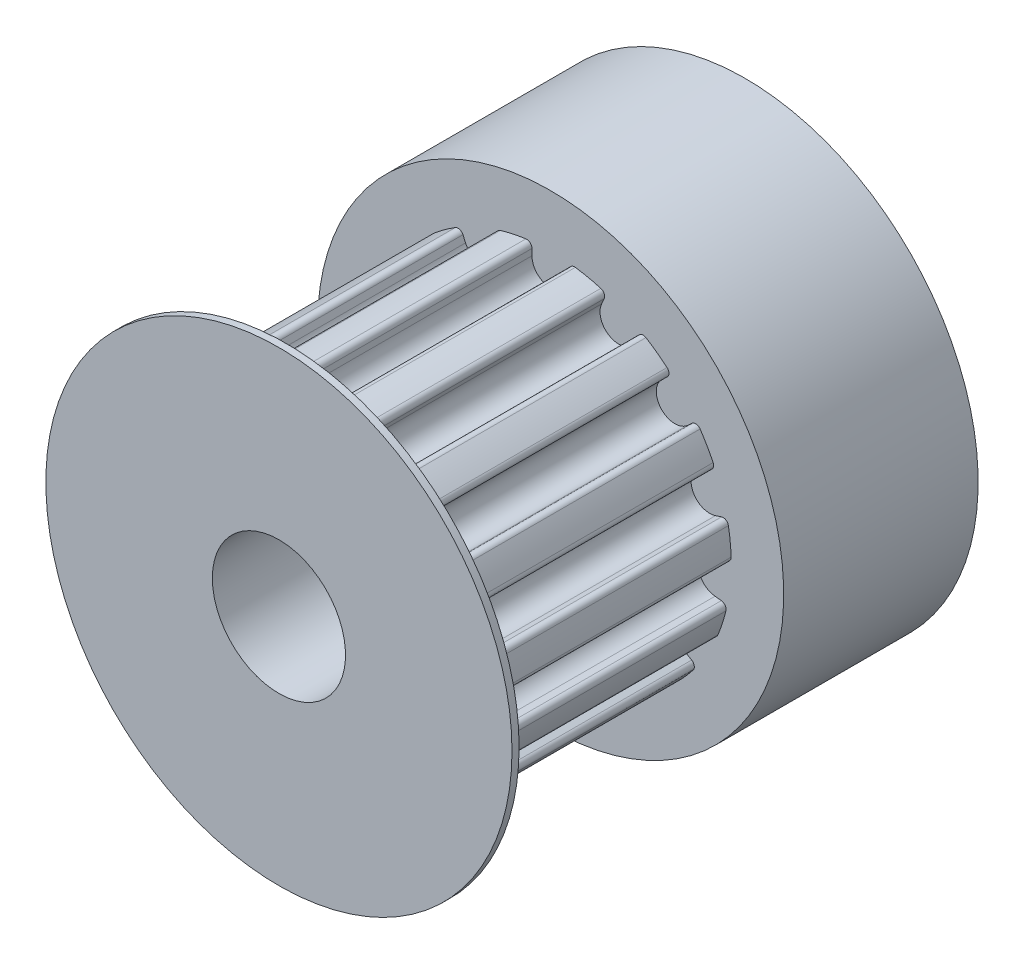
SolidWorks part; units mm, degrees
ref_plane "Front" through (0, 0, 0) normal (0, 0, 1) x (1, 0, 0)
ref_plane "Top" through (0, 0, 0) normal (0, 1, 0) x (1, 0, 0)
ref_plane "Right" through (0, 0, 0) normal (1, 0, 0) x (0, 0, -1)
sketch "support-front-body" plane through (0, 0, 0) normal (0, 0, 1) x (1, 0, 0)
  line L0 (0, 0) -> (0, 6.78) construction
  line L1 (0, 0) -> (0, -6.78) construction
  line L2 (0, 0) -> (6.78, 0) construction
  line L3 (0, 0) -> (-6.78, 0) construction
  circle A0 centre (0, 0) radius 6.78
  dimension "diam-outer" = 13.56
sketch "support-right-body" plane through (0, 0, 0) normal (1, 0, 0) x (0, 0, -1)
  line L0 (0, 0) -> (10.2, 0) construction
  line L1 (0, 6.78) -> (10.2, 6.78)
  line L2 (0, 6.78) -> (0, -6.78)
  line L3 (0, -6.78) -> (10.2, -6.78)
  line L4 (10.2, 6.78) -> (10.2, -6.78)
  dimension "length" = 10.2
sketch "support-right-chamfer" plane through (0, 0, 0) normal (1, 0, 0) x (0, 0, -1)
  line L0 (0, 0) -> (10.2, 0) construction
  line L1 (0, -6.78) -> (0, -5.78)
  line L2 (0, 6.78) -> (0, -6.78) construction
  line L4 (0, -5.78) -> (1, -6.78)
  line L5 (0, -6.78) -> (10.2, -6.78) construction
  line L7 (1, -6.78) -> (0, -6.78)
  line L9 (10.2, -6.78) -> (9.2, -6.78)
  line L11 (9.2, -6.78) -> (10.2, -5.78)
  line L12 (10.2, 6.78) -> (10.2, -6.78) construction
  line L14 (10.2, -5.78) -> (10.2, -6.78)
  dimension "height-chamfer-front" = 1
  dimension "angle-chamfer-front" = 45
  dimension "angle-chamfer-back" = 45
  dimension "height-chamfer-back" = 1
sketch "support-right-hub" plane through (0, 0, 0) normal (1, 0, 0) x (0, 0, -1)
  line L0 (17.5, 0) -> (10.2, 0) construction
  line L1 (10.2, 8.75) -> (17.5, 8.75)
  line L2 (10.2, 8.75) -> (10.2, -8.75)
  line L3 (10.2, -8.75) -> (17.5, -8.75)
  line L4 (17.5, 8.75) -> (17.5, -8.75)
  line L6 (0, 0) -> (10.2, 0) construction
  line L8 (0, 6.78) -> (0, -6.78) construction
  dimension "diam-hub" = 17.5
  dimension "length-hub" = 7.3
  dimension "dist-hub" = 10.2
sketch "support-right-bore" plane through (0, 0, 0) normal (1, 0, 0) x (0, 0, -1)
  line L0 (0, 6.78) -> (0, -6.78) construction
  line L1 (0, 0.5) -> (17.5, 0.5)
  line L2 (0, 0.5) -> (0, -0.5)
  line L3 (0, -0.5) -> (17.5, -0.5)
  line L4 (17.5, 0.5) -> (17.5, 0)
  line L5 (17.5, 0) -> (0, 0) construction
  line L6 (0, 0) -> (10.2, 0) construction
  line L7 (17.5, 0) -> (17.5, -0.5)
  line L8 (17.5, -0.5) -> (17.5, 0.5) construction
  dimension "diam-bore" = 1
  dimension "length-bore" = 17.5
  dimension "angle-bore-bottom" = 180
  dimension "angle-bore" = 90
sketch "support-stop-screw-hole" plane through (0, 0, 0) normal (1, 0, 0) x (0, 0, -1)
  line L1 (6.5667, 11) -> (9.4333, 11)
  line L2 (6.5667, 11) -> (6.5667, -1)
  line L3 (8, -1) -> (9.4333, -1)
  line L4 (9.4333, 11) -> (9.4333, -1)
  line L5 (8, -1) -> (8, 11) construction
  line L6 (8, -1) -> (6.5667, -1)
  line L7 (0, 0) -> (8, 0) construction
  line L8 (0, 6.78) -> (0, -6.78) construction
  dimension "diam-stop-screw-hole" = 2.8665
  dimension "dist-stop-screw-hole" = 8
  dimension "depth-stop-screw-hole" = 12
  dimension "angle-stop-screw-hole" = 180
  dimension "height-stop-screw-hole" = 11
sketch "support-front-keygroove" plane through (0, 0, 0) normal (0, 0, 1) x (1, 0, 0)
  line L0 (0, 0) -> (0, -0.5) construction
  line L1 (-1, 7.5) -> (1, 7.5)
  line L2 (-1, 7.5) -> (-1, 5.3)
  line L3 (-1, 5.3) -> (1, 5.3)
  line L4 (1, 7.5) -> (1, 5.3)
  line L5 (0, 0) -> (0, 0.5) construction
  circle A0 centre (0, 0) radius 0.5 construction
  dimension "width-keygroove" = 2
  dimension "dist-keygroove" = 8
  dimension "height-keygroove" = 2.2
sketch "support-front-tooth" plane through (0, 0, 0) normal (0, 0, 1) x (1, 0, 0)
  line L0 (0.7, 6.28) -> (0.7, 6.5182)
  line L1 (0, 0) -> (0, 6.78) construction
  line L2 (-0.7, 6.28) -> (-0.7, 6.5182)
  line L3 (0, 6.7163) -> (0, 6.78) construction
  line L8 (0, 6.7163) -> (0, 5.58) construction
  line L9 (0.9274, 6.7163) -> (-0.9274, 6.7163) construction
  line L10 (0, 6.7163) -> (0, 7.8526) construction
  line L17 (0.9274, 6.7163) -> (0.9274, 7.8526)
  line L21 (-0.9274, 7.8526) -> (-0.9274, 6.7163)
  line L22 (0.9274, 7.8526) -> (-0.9274, 7.8526)
  arc A0 (-0.7, 6.28) -> (0.7, 6.28) centre (0, 6.28) ccw
  circle A1 centre (0, 0) radius 6.78 construction
  arc A2 (0.7, 6.5182) -> (0.9274, 6.7163) centre (0.9, 6.5182) cw
  arc A3 (-0.7, 6.5182) -> (-0.9274, 6.7163) centre (-0.9, 6.5182) ccw
  circle A4 centre (0, 0) radius 6.78
  dimension "D3" = 0.2
  dimension "D2" = 0.7
  dimension "D1" = 1.2
sketch "support-right-flange" plane through (0, 0, 0) normal (1, 0, 0) x (0, 0, -1)
  line L0 (0, 3.392) -> (0, 6.964)
  line L1 (10.2, 6.78) -> (10.2, -6.78) construction
  line L2 (0, 6.964) -> (0.5, 6.964) construction
  line L3 (0.5, 6.964) -> (0.5, 8.75)
  line L4 (0, 8.75) -> (0.5, 8.75)
  line L5 (0.5, 6.964) -> (0.5, 3.392)
  line L6 (0.5, 3.392) -> (0, 3.392)
  line L7 (5.1, 6.78) -> (5.1, 0) construction
  line L8 (0, 6.78) -> (10.2, 6.78) construction
  line L9 (0, 6.964) -> (0, 8.75)
  line L10 (9.7, 3.392) -> (10.2, 3.392)
  line L11 (9.7, 6.964) -> (9.7, 3.392)
  line L12 (10.2, 8.75) -> (9.7, 8.75)
  line L13 (9.7, 6.964) -> (9.7, 8.75)
  line L14 (10.2, 6.964) -> (10.2, 8.75)
  line L15 (10.2, 3.392) -> (10.2, 6.964)
  line L16 (10.2, 0) -> (0, 0) construction
  line L17 (10.2, -3.392) -> (10.2, -6.964)
  line L18 (10.2, -6.964) -> (10.2, -8.75)
  line L19 (9.7, -6.964) -> (9.7, -8.75)
  line L20 (10.2, -8.75) -> (9.7, -8.75)
  line L21 (9.7, -6.964) -> (9.7, -3.392)
  line L22 (9.7, -3.392) -> (10.2, -3.392)
  line L23 (0.5, -3.392) -> (0, -3.392)
  line L24 (0.5, -6.964) -> (0.5, -3.392)
  line L25 (0, -8.75) -> (0.5, -8.75)
  line L26 (0.5, -6.964) -> (0.5, -8.75)
  line L27 (0, -6.964) -> (0, -8.75)
  line L28 (0, -3.392) -> (0, -6.964)
  line L29 (0, 0) -> (10.2, 0) construction
  line L30 (0, 6.964) -> (0.5, 6.964) construction
  line L31 (0.25, 3.392) -> (0.25, 5.178) construction
  line L32 (0.25, 5.178) -> (0.25, 6.964) construction
  line L33 (0.25, 8.75) -> (0.25, 6.964) construction
  line L34 (0, 6.78) -> (10.2, 6.78) construction
  dimension "angle-flange" = 180
  dimension "thickness-flange" = 0.5
  dimension "diam-flange-inner" = 6.784
  dimension "diam-flange-outer" = 17.5
  dimension "width-flange-inner" = 9.2
sketch "support-right-flange-profile" plane through (0, 0, 0) normal (1, 0, 0) x (0, 0, -1)
  line L0 (0.2668, 8.75) -> (0.5, 8.75)
  line L2 (0.5, 8.75) -> (0.5, 8.25)
  line L3 (0.5, 6.964) -> (0.5, 3.392) construction
  line L4 (0.5, 8.25) -> (0.2668, 8.75)
  line L5 (0, 0) -> (10.2, 0) construction
  line L6 (5.1, 0) -> (5.1, 6.78) construction
  line L7 (9.7, 8.25) -> (9.9332, 8.75)
  line L8 (9.7, 8.75) -> (9.7, 8.25)
  line L9 (9.9332, 8.75) -> (9.7, 8.75)
  dimension "D1" = 25
  dimension "D2" = 0.5
ref_axis "ref-axis-center" through (0, 0, -10.2) along (0, 0, 1)
ref_plane "ref-plane-front" through (0, 0, 0) normal (0, 0, 1) x (1, 0, 0)
ref_plane "ref-plane-back" through (0, 0, -10.2) normal (0, 0, 1) x (1, 0, 0)
ref_plane "ref-plane-hub-front" through (0, 0, -10.2) normal (0, 0, 1) x (1, 0, 0)
ref_plane "ref-plane-hub-back" through (0, 0, -17.5) normal (0, 0, 1) x (1, 0, 0)
ref_plane "ref-plane-bore-front" through (0, 0, 0) normal (0, 0, 1) x (1, 0, 0)
ref_plane "ref-plane-bore-back" through (0, 0, -17.5) normal (0, 0, 1) x (1, 0, 0)
ref_plane "ref-plane-stop-screw-hole-top" through (0, 11, 0) normal (0, 1, 0) x (-1, 0, 0)
ref_axis "ref-axis-stop-screw-hole" through (0, 11, -8) along (0, -1, 0)
sketch "Sketch5" plane through (0, 0, 0) normal (1, 0, 0) x (0, 0, -1)
  line L0 (10.2, 6.78) -> (10.2, -6.78) construction
  line L1 (0, 6.78) -> (10.2, 6.78) construction
  line L2 (0, 6.78) -> (0, -6.78) construction
  line L3 (0, 0) -> (10.2, 0) construction
  line L4 (10.2, 6.78) -> (10.2, 0)
  line L5 (0, 6.78) -> (10.2, 6.78)
  line L6 (0, 6.78) -> (0, 0)
  line L7 (0, 0) -> (10.2, 0) construction
  line L8 (0, 0) -> (10.2, 0)
revolve "body" add sketch "Sketch5" angle 360 about L7
sketch "Sketch11" plane through (0, 0, 0) normal (1, 0, 0) x (0, 0, -1)
  line L0 (0, -6.78) -> (0, -5.78) construction
  line L3 (1, -6.78) -> (0, -6.78) construction
  line L5 (0, -5.78) -> (1, -6.78) construction
  line L8 (0, -6.78) -> (0, -5.78)
  line L9 (1, -6.78) -> (0, -6.78)
  line L10 (0, -5.78) -> (1, -6.78)
  line L11 (0, 0) -> (10.2, 0) construction
  line L12 (0, 0) -> (10.2, 0) construction
revolve "cut-chamfer-front" [suppressed] cut sketch "Sketch11" angle 360 about L12
sketch "Sketch13" plane through (0, 0, 0) normal (1, 0, 0) x (0, 0, -1)
  line L0 (0, 0) -> (10.2, 0) construction
  line L1 (10.2, -6.78) -> (9.2, -6.78) construction
  line L2 (10.2, -5.78) -> (10.2, -6.78) construction
  line L3 (9.2, -6.78) -> (10.2, -5.78) construction
  line L4 (0, 0) -> (10.2, 0) construction
  line L5 (10.2, -6.78) -> (9.2, -6.78)
  line L6 (10.2, -5.78) -> (10.2, -6.78)
  line L7 (9.2, -6.78) -> (10.2, -5.78)
revolve "cut-chamfer-back" [suppressed] cut sketch "Sketch13" angle 360 about L4
sketch "Sketch16" plane through (0, 0, 0) normal (1, 0, 0) x (0, 0, -1)
  line L0 (17.5, 8.75) -> (17.5, -8.75) construction
  line L1 (10.2, 8.75) -> (17.5, 8.75) construction
  line L2 (17.5, 0) -> (10.2, 0) construction
  line L3 (10.2, 8.75) -> (10.2, -8.75) construction
  line L4 (17.5, 8.75) -> (17.5, 0)
  line L5 (10.2, 8.75) -> (17.5, 8.75)
  line L6 (17.5, 0) -> (10.2, 0) construction
  line L7 (10.2, 8.75) -> (10.2, 0)
  line L8 (17.5, 0) -> (10.2, 0)
revolve "body-hub" add sketch "Sketch16" angle 360 about L6
sketch "Sketch17" plane through (0, 0, 0) normal (1, 0, 0) x (0, 0, -1)
  line L0 (17.5, 0.5) -> (17.5, 0) construction
  line L1 (17.5, 0) -> (0, 0) construction
  line L2 (0, 0.5) -> (17.5, 0.5) construction
  line L3 (0, 0.5) -> (0, -0.5) construction
  line L4 (17.5, 0.5) -> (17.5, 0)
  line L5 (17.5, 0) -> (0, 0) construction
  line L6 (0, 0.5) -> (17.5, 0.5)
  line L7 (0, 0.5) -> (0, 0)
  line L8 (17.5, 0) -> (0, 0)
revolve "body-bore" [suppressed] cut sketch "Sketch17" angle 360 about L5
sketch "Sketch19" plane through (0, 0, 0) normal (1, 0, 0) x (0, 0, -1)
  line L0 (6.5667, 11) -> (9.4333, 11) construction
  line L1 (8, -1) -> (8, 11) construction
  line L2 (9.4333, 11) -> (9.4333, -1) construction
  line L3 (8, -1) -> (9.4333, -1) construction
  line L4 (8, 11) -> (9.4333, 11)
  line L5 (8, -1) -> (8, 11) construction
  line L6 (9.4333, 11) -> (9.4333, -1)
  line L7 (8, -1) -> (9.4333, -1)
  line L8 (8, -1) -> (8, 11)
revolve "body-stop-screw-hole" [suppressed] cut sketch "Sketch19" angle 360 about L5
pattern_circular "pattern-stop-screw-hole" [suppressed] count 2 every 90 about axis through (0, 0, -10.2) along (0, 0, 1) reverse direction yes
sketch "Sketch21" plane through (0, 0, 0) normal (0, 0, 1) x (1, 0, 0)
  line L0 (-1, 7.5) -> (1, 7.5) construction
  line L1 (-1, 7.5) -> (-1, 5.3) construction
  line L2 (-1, 5.3) -> (1, 5.3) construction
  line L3 (1, 7.5) -> (1, 5.3) construction
  line L4 (-1, 7.5) -> (1, 7.5)
  line L5 (-1, 7.5) -> (-1, 5.3)
  line L6 (-1, 5.3) -> (1, 5.3)
  line L7 (1, 7.5) -> (1, 5.3)
extrude "cut-keygroove" [suppressed] cut sketch "Sketch21" against normal up to surface (17.5 mm away)
sketch "Sketch23" plane through (0, 0, 0) normal (0, 0, 1) x (1, 0, 0)
  line L5 (0.7, 6.28) -> (0.7, 6.5182)
  line L6 (0.7, 6.28) -> (0.7, 6.5182)
  line L7 (-0.7, 6.5182) -> (-0.7, 6.28)
  line L8 (-0.7, 6.5182) -> (-0.7, 6.28)
  line L9 (0.9274, 6.7163) -> (0.9274, 7.8526)
  line L13 (-0.9274, 7.8526) -> (-0.9274, 6.7163)
  line L14 (0.9274, 7.8526) -> (-0.9274, 7.8526)
  line L15 (0.9274, 6.7163) -> (0.9274, 7.8526)
  line L19 (-0.9274, 7.8526) -> (-0.9274, 6.7163)
  line L20 (0.9274, 7.8526) -> (-0.9274, 7.8526)
  arc A3 (0.9274, 6.7163) -> (0.7, 6.5182) centre (0.9, 6.5182) ccw
  arc A4 (0.9274, 6.7163) -> (0.7, 6.5182) centre (0.9, 6.5182) ccw
  arc A5 (-0.7, 6.28) -> (0.7, 6.28) centre (0, 6.28) ccw
  arc A6 (-0.7, 6.28) -> (0.7, 6.28) centre (0, 6.28) ccw
  arc A7 (-0.7, 6.5182) -> (-0.9274, 6.7163) centre (-0.9, 6.5182) ccw
  arc A8 (-0.7, 6.5182) -> (-0.9274, 6.7163) centre (-0.9, 6.5182) ccw
  dimension "D1" = 0
extrude "cut-tooth" cut sketch "Sketch23" against normal up to surface (10.2 mm away) up to plane "ref-plane-back"
pattern_circular "pattern-tooth" count 15 over 360 about axis through (0, 0, -10.2) along (0, 0, 1) of "cut-tooth"
sketch "Sketch25" plane through (0, 0, 0) normal (1, 0, 0) x (0, 0, -1)
  line L0 (0, 0) -> (10.2, 0) construction
  line L1 (0.5, 3.392) -> (0, 3.392) construction
  line L2 (0.5, 6.964) -> (0.5, 3.392) construction
  line L4 (0, 8.75) -> (0.5, 8.75) construction
  line L5 (0, 6.964) -> (0, 8.75) construction
  line L6 (0, 3.392) -> (0, 6.964) construction
  line L7 (0, 0) -> (10.2, 0) construction
  line L8 (0.5, 3.392) -> (0, 3.392)
  line L9 (0.5, 6.964) -> (0.5, 3.392)
  line L10 (0, 8.75) -> (0.5, 8.75)
  line L11 (0.5, 6.964) -> (0.5, 8.75) construction
  line L12 (0, 6.964) -> (0, 8.75)
  line L13 (0, 3.392) -> (0, 6.964)
  line L14 (0.5, 6.964) -> (0.5, 8.75)
revolve "body-flange-front" add sketch "Sketch25" angle 360 about L7
sketch "Sketch26" plane through (0, 0, 0) normal (1, 0, 0) x (0, 0, -1)
  line L0 (10.2, 0) -> (0, 0) construction
  line L1 (9.7, 3.392) -> (10.2, 3.392) construction
  line L2 (9.7, 6.964) -> (9.7, 3.392) construction
  line L4 (10.2, 8.75) -> (9.7, 8.75) construction
  line L5 (10.2, 6.964) -> (10.2, 8.75) construction
  line L6 (10.2, 3.392) -> (10.2, 6.964) construction
  line L7 (10.2, 0) -> (0, 0) construction
  line L8 (9.7, 3.392) -> (10.2, 3.392)
  line L9 (9.7, 6.964) -> (9.7, 3.392)
  line L10 (10.2, 8.75) -> (9.7, 8.75)
  line L11 (9.7, 6.964) -> (9.7, 8.75) construction
  line L12 (10.2, 6.964) -> (10.2, 8.75)
  line L13 (10.2, 3.392) -> (10.2, 6.964)
  line L14 (9.7, 6.964) -> (9.7, 8.75)
revolve "body-flange-back" [suppressed] add sketch "Sketch26" angle 360 about L7
sketch "Sketch28" plane through (0, 0, 0) normal (1, 0, 0) x (0, 0, -1)
  line L0 (0.5, 8.75) -> (0.5, 8.25) construction
  line L1 (0.2668, 8.75) -> (0.5, 8.75) construction
  line L2 (0.5, 8.25) -> (0.2668, 8.75) construction
  line L3 (0.5, 8.75) -> (0.5, 8.25)
  line L4 (0.2668, 8.75) -> (0.5, 8.75)
  line L5 (0.5, 8.25) -> (0.2668, 8.75)
  line L6 (10.2, 0) -> (0, 0) construction
  line L7 (10.2, 0) -> (0, 0) construction
revolve "body-flange-profile-front" cut sketch "Sketch28" angle 360 about L7
sketch "Sketch29" plane through (0, 0, 0) normal (1, 0, 0) x (0, 0, -1)
  line L0 (10.2, 0) -> (0, 0) construction
  line L1 (9.7, 8.75) -> (9.7, 8.25) construction
  line L2 (9.9332, 8.75) -> (9.7, 8.75) construction
  line L3 (9.7, 8.25) -> (9.9332, 8.75) construction
  line L4 (10.2, 0) -> (0, 0) construction
  line L5 (9.7, 8.75) -> (9.7, 8.25)
  line L6 (9.9332, 8.75) -> (9.7, 8.75)
  line L7 (9.7, 8.25) -> (9.9332, 8.75)
revolve "body-flange-profile-back" [suppressed] cut sketch "Sketch29" angle 360 about L4
sketch "support-right-cut-body" plane through (0, 0, 0) normal (1, 0, 0) x (0, 0, -1)
  line L0 (10.2, 6.78) -> (10.2, -6.78) construction
  line L1 (0, 6.78) -> (10.2, 6.78) construction
  line L2 (0, 6.78) -> (0, -6.78) construction
  line L3 (0, -6.78) -> (10.2, -6.78) construction
  line L4 (10.2, 6.78) -> (10.2, -6.78) construction
  line L5 (0, 6.78) -> (0, -6.78) construction
  line L6 (0, 6.78) -> (10.2, 6.78) construction
  line L7 (0, -6.78) -> (10.2, -6.78) construction
  line L8 (10.2, 0) -> (0, 0) construction
  line L9 (5.1, 6.78) -> (5.1, -6.78) construction
  line L10 (10.2, 5.08) -> (6.8, 5.08)
  line L11 (10.2, 5.08) -> (10.2, -5.08)
  line L12 (10.2, -5.08) -> (6.8, -5.08)
  line L13 (6.8, 5.08) -> (6.8, -5.08)
  line L14 (0, 5.08) -> (3.4, 5.08)
  line L15 (0, 5.08) -> (0, -5.08)
  line L16 (0, -5.08) -> (3.4, -5.08)
  line L17 (3.4, 5.08) -> (3.4, -5.08)
  line L18 (6.8, 5.08) -> (3.4, 5.08) construction
  line L19 (3.4, -5.08) -> (5.1, -5.08) construction
  line L20 (3.4, -5.08) -> (3.4, -6.78) construction
  line L21 (10.2, 8.75) -> (6.8, 8.75)
  line L23 (10.2, 8.75) -> (17.5, 8.75) construction
  line L24 (10.2, -8.75) -> (6.8, -8.75)
  line L25 (0, 8.75) -> (3.4, 8.75)
  line L26 (0, -8.75) -> (3.4, -8.75)
sketch "Sketch31" plane through (0, 0, 0) normal (1, 0, 0) x (0, 0, -1)
  line L0 (0, 5.08) -> (0, -5.08) construction
  line L1 (0, 5.08) -> (3.4, 5.08) construction
  line L2 (3.4, 5.08) -> (3.4, -5.08) construction
  line L3 (10.2, 5.08) -> (10.2, -5.08) construction
  line L4 (10.2, 5.08) -> (6.8, 5.08) construction
  line L5 (6.8, 5.08) -> (6.8, -5.08) construction
  line L7 (0, 5.08) -> (0, 8.75)
  line L8 (0, 5.08) -> (3.4, 5.08)
  line L9 (3.4, 5.08) -> (3.4, 8.75)
  line L10 (10.2, 5.08) -> (10.2, 8.75)
  line L11 (10.2, 5.08) -> (6.8, 5.08)
  line L12 (6.8, 5.08) -> (6.8, 8.75)
  line L13 (10.2, 8.75) -> (6.8, 8.75)
  line L14 (10.2, 8.75) -> (6.8, 8.75) construction
  line L15 (3.4, 8.75) -> (0, 8.75)
  line L16 (0, 0) -> (10.2, 0) construction
  line L17 (10.2, 0) -> (0, 0) construction
revolve "cut-body" [suppressed] cut sketch "Sketch31" angle 360 about L16
sketch "草图1" plane through (0, 0, -17.5) normal (0, 0, -1) x (-1, 0, 0)
  circle A0 centre (0, 0) radius 2.5
  dimension "D1" = 5
extrude "切除-拉伸1" cut sketch "草图1" against normal blind 20
sketch "草图2" plane through (0, 0, 0) normal (0, 1, 0) x (1, 0, 0)
  circle A0 centre (0, 14) radius 1
  dimension "D1" = 2
  dimension "D2" = 3.5
extrude "切除-拉伸2" cut sketch "草图2" against normal blind 10
